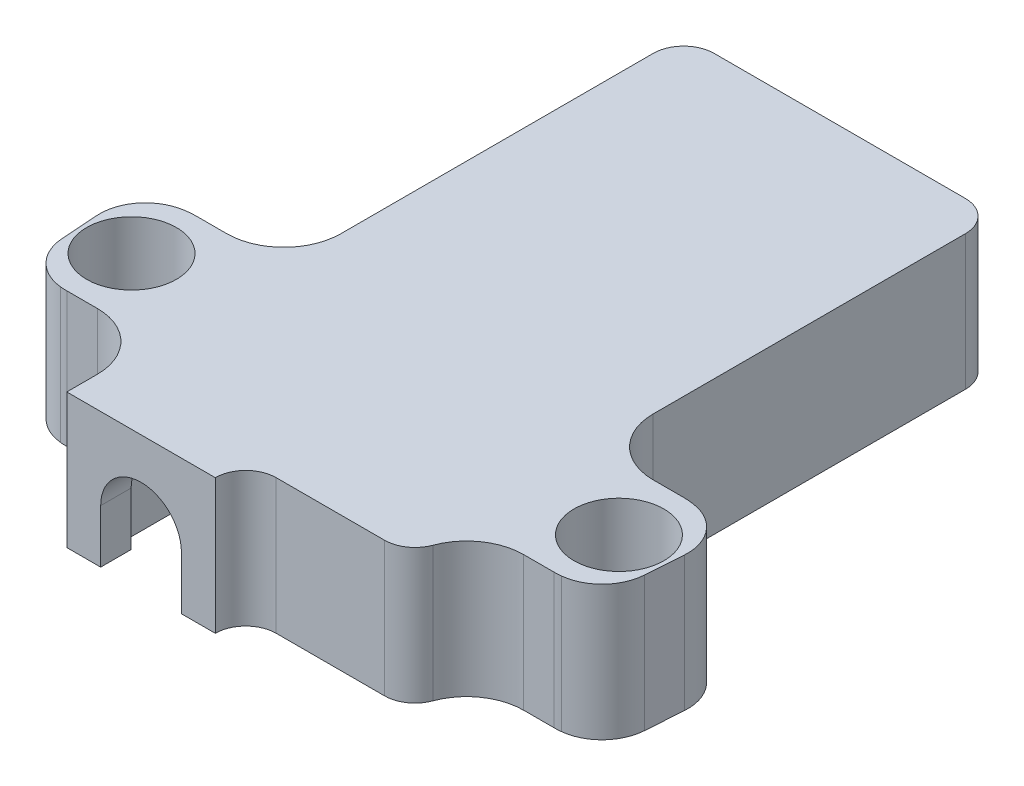
SolidWorks part; units mm, degrees
ref_plane "Front Plane" through (0, 0, 0) normal (0, 0, 1) x (1, 0, 0)
ref_plane "Top Plane" through (0, 0, 0) normal (0, 1, 0) x (1, 0, 0)
ref_plane "Right Plane" through (0, 0, 0) normal (1, 0, 0) x (0, 0, -1)
sketch "Sketch1" plane through (0, 0, 0) normal (0, 1, 0) x (1, 0, 0)
  line L0 (-24.2603, 0) -> (21.0129, 0) construction
  line L1 (0, 32.3789) -> (0, -20.9174) construction
  line L2 (0, 30.5) -> (0, -8) construction
  line L3 (-10.25, 30.5) -> (10.25, 30.5)
  line L4 (-10.25, 30.5) -> (-10.25, -8)
  line L5 (-10.25, -8) -> (10.25, -8)
  line L6 (10.25, 30.5) -> (10.25, -8)
  line L7 (-16, 4.25) -> (-10.25, 4.25)
  line L8 (-16, -4.25) -> (-10.25, -4.25)
  line L9 (16, 4.25) -> (10.25, 4.25)
  line L10 (16, -4.25) -> (10.25, -4.25)
  circle A0 centre (-16, 0) radius 1.75
  circle A1 centre (16, 0) radius 1.75
  circle A2 centre (-16, 0) radius 4.25
  circle A3 centre (16, 0) radius 4.25
  dimension "D1" = 3.5
  dimension "D2" = 32
  dimension "D3" = 20.5
  dimension "D5" = 8
  dimension "D6" = 38.5
  dimension "D4" = 2.5
extrude "Boss-Extrude1" add sketch "Sketch1" along normal blind 1.5 contours L6 L3 L4 L5 | A2 L8 L4 L7 | A2 A0 | L10 A3 L9 L6 | A3 A1
sketch "Sketch2" plane through (0, 1.5, 0) normal (0, 1, 0) x (1, 0, 0)
  line L1 (-10.25, 30.5) -> (10.25, 30.5)
  line L2 (-10.25, 30.5) -> (-10.25, -8)
  line L3 (-10.25, -8) -> (10.25, -8)
  line L4 (10.25, 30.5) -> (10.25, -8)
extrude "Boss-Extrude2" add sketch "Sketch2" along normal offset from surface (7.35 mm away) 8.85 up to face at (0, 0, -3.75)
sketch "Sketch3" plane through (0, 0, 0) normal (0, -1, 0) x (1, 0, 0)
  line L0 (-10.25, 8) -> (10.25, 8) construction
  line L1 (-8.75, 6.5) -> (8.75, 6.5)
  line L2 (-8.75, 6.5) -> (-8.75, -29)
  line L3 (-8.75, -29) -> (8.75, -29)
  line L4 (8.75, 6.5) -> (8.75, -29)
  line L5 (-10.25, -30.5) -> (10.25, -30.5) construction
  line L6 (-10.25, -30.5) -> (-10.25, -4.25) construction
  line L7 (10.25, -30.5) -> (10.25, -4.25) construction
  line L8 (-8.75, 6.5) -> (-8.75, 8)
  line L9 (-2, 6.5) -> (-2, 8)
  line M8 (10.25, 8) -> (-10.25, 8)
  dimension "D1" = 1.5
  dimension "D2" = 1.5
  dimension "D3" = 1.5
  dimension "D4" = 1.5
  dimension "D5" = 6.75
extrude "Cut-Extrude1" cut sketch "Sketch3" against normal offset from surface (7.35 mm away) 1.5 contours L4 L1 L2 L3 | L1 L9 L8 M8 up to face at (0, 8.85, -11.25)
sketch "Sketch4" plane through (0, 0, 0) normal (0, -1, 0) x (1, 0, 0)
  line L0 (-6.45, -29) -> (-6.45, -30.5)
  line L1 (-8.75, -29) -> (8.75, -29) construction
  line L2 (-10.25, -30.5) -> (10.25, -30.5) construction
  line L3 (0.75, -29) -> (0.75, -30.5)
  line L4 (-8.75, 8) -> (-8.75, -29) construction
  line L5 (-6.45, -29) -> (0.75, -29)
  line L6 (-6.45, -30.5) -> (0.75, -30.5)
  dimension "D1" = 2.3
  dimension "D2" = 7.2
extrude "Cut-Extrude2" cut sketch "Sketch4" against normal offset from surface (4.05 mm away) 3.3 up to face at (-0.6667, 7.35, -4.8333)
sketch "Sketch6" plane through (0, 7.35, 0) normal (0, -1, 0) x (1, 0, 0)
  line L0 (8.75, 6.5) -> (8.75, -29) construction
  line L1 (-8.75, -29) -> (8.75, -29)
  line L2 (-8.75, -29) -> (-8.75, -27.5)
  line L3 (-8.75, -27.5) -> (8.75, -27.5)
  line L4 (8.75, -29) -> (8.75, -27.5)
  dimension "D1" = 1.5
extrude "Boss-Extrude3" add sketch "Sketch6" along normal blind 1.35
sketch "Sketch7" plane through (0, 0, -29) normal (0, 0, 1) x (1, 0, 0)
  line L0 (8.75, 6) -> (8.75, 0) construction
  line L1 (8.75, 4.25) -> (5.25, 4.25)
  line L2 (8.75, 4.25) -> (8.75, 2.25)
  line L3 (8.75, 2.25) -> (5.25, 2.25)
  line L4 (5.25, 4.25) -> (5.25, 2.25)
  line L5 (-8.75, 6) -> (8.75, 6) construction
  dimension "D1" = 1.75
  dimension "D2" = 3.5
  dimension "D3" = 2
extrude "Boss-Extrude4" add sketch "Sketch7" along normal blind 1
sketch "Sketch8" plane through (0, 1.5, 0) normal (0, 1, 0) x (1, 0, 0)
  line L3 (-10.25, -4.25) -> (-10.25, 4.25)
  line L4 (-10.25, 4.25) -> (-16, 4.25)
  line L5 (-16, -4.25) -> (-10.25, -4.25)
  line L6 (-10.25, -4.25) -> (-10.25, 4.25)
  line L7 (-10.25, 4.25) -> (-16, 4.25)
  line L8 (-16, -4.25) -> (-10.25, -4.25)
  line L9 (10.25, 4.25) -> (10.25, -4.25)
  line L10 (10.25, -4.25) -> (16, -4.25)
  line L11 (16, 4.25) -> (10.25, 4.25)
  line L12 (10.25, 4.25) -> (10.25, -4.25)
  line L13 (10.25, -4.25) -> (16, -4.25)
  line L14 (16, 4.25) -> (10.25, 4.25)
  circle A0 centre (-16, 0) radius 2.95
  circle A1 centre (16, 0) radius 2.95
  arc A5 (-16, 4.25) -> (-16, -4.25) centre (-16, 0) ccw
  arc A8 (-16, 4.25) -> (-16, -4.25) centre (-16, 0) ccw
  arc A11 (16, -4.25) -> (16, 4.25) centre (16, 0) ccw
  arc A14 (16, -4.25) -> (16, 4.25) centre (16, 0) ccw
  dimension "D1" = 5.9
  dimension "D2" = 0
  dimension "D3" = 0
extrude "Boss-Extrude5" add sketch "Sketch8" along normal up to surface (7.35 mm away)
fillet "Fillet2" radius 3.75 4 edges
sketch "Sketch9" plane through (0, 8.85, 0) normal (0, 1, 0) x (1, 0, 0)
  line L0 (-24.9829, 53.6863) -> (-20.9528, -3.9479)
  line L1 (-15.1854, -10.3533) -> (-1.2155, -12.8165)
  line L2 (1.2155, -12.8165) -> (15.1854, -10.3533)
  line L3 (20.9528, -3.9479) -> (24.9829, 53.6863)
  line L4 (25, 54.1746) -> (25, 107.8254)
  line L5 (24.9829, 108.3137) -> (20.9528, 165.9479)
  line L6 (15.1854, 172.3533) -> (1.2155, 174.8165)
  line L7 (-1.2155, 174.8165) -> (-15.1854, 172.3533)
  line L8 (-20.9528, 165.9479) -> (-24.9829, 108.3137)
  line L9 (-25, 107.8254) -> (-25, 54.1746)
  line L10 (-18.9576, 165.8084) -> (-22.9878, 108.1742)
  line L11 (-23, 107.8254) -> (-23, 54.1746)
  line L12 (-22.9878, 53.8258) -> (-18.9576, -3.8084)
  line L13 (-14.8381, -8.3836) -> (-0.8682, -10.8469)
  line L14 (0.8682, -10.8469) -> (14.8381, -8.3836)
  line L15 (18.9576, -3.8084) -> (22.9878, 53.8258)
  line L16 (23, 54.1746) -> (23, 107.8254)
  line L17 (22.9878, 108.1742) -> (18.9576, 165.8084)
  line L18 (14.8381, 170.3836) -> (0.8682, 172.8469)
  line L19 (-0.8682, 172.8469) -> (-14.8381, 170.3836)
  line L20 (-18.9576, 165.8084) -> (-22.9878, 108.1742)
  line L21 (-23, 107.8254) -> (-23, 54.1746)
  line L22 (-22.9878, 53.8258) -> (-18.9576, -3.8084)
  line L23 (-14.8381, -8.3836) -> (-0.8682, -10.8469)
  line L24 (0.8682, -10.8469) -> (14.8381, -8.3836)
  line L25 (18.9576, -3.8084) -> (22.9878, 53.8258)
  line L26 (23, 54.1746) -> (23, 107.8254)
  line L27 (22.9878, 108.1742) -> (18.9576, 165.8084)
  line L28 (14.8381, 170.3836) -> (0.8682, 172.8469)
  line L29 (-0.8682, 172.8469) -> (-14.8381, 170.3836)
  arc A0 (-20.9528, -3.9479) -> (-15.1854, -10.3533) centre (-13.9698, -3.4596) ccw
  arc A1 (-1.2155, -12.8165) -> (1.2155, -12.8165) centre (0, -5.9229) ccw
  arc A2 (15.1854, -10.3533) -> (20.9528, -3.9479) centre (13.9698, -3.4596) ccw
  arc A3 (24.9829, 53.6863) -> (25, 54.1746) centre (18, 54.1746) ccw
  arc A4 (25, 107.8254) -> (24.9829, 108.3137) centre (18, 107.8254) ccw
  arc A5 (20.9528, 165.9479) -> (15.1854, 172.3533) centre (13.9698, 165.4596) ccw
  arc A6 (1.2155, 174.8165) -> (-1.2155, 174.8165) centre (0, 167.9229) ccw
  arc A7 (-15.1854, 172.3533) -> (-20.9528, 165.9479) centre (-13.9698, 165.4596) ccw
  arc A8 (-24.9829, 108.3137) -> (-25, 107.8254) centre (-18, 107.8254) ccw
  arc A9 (-25, 54.1746) -> (-24.9829, 53.6863) centre (-18, 54.1746) ccw
  arc A10 (-14.8381, 170.3836) -> (-18.9576, 165.8084) centre (-13.9698, 165.4596) ccw
  arc A11 (-22.9878, 108.1742) -> (-23, 107.8254) centre (-18, 107.8254) ccw
  arc A12 (-23, 54.1746) -> (-22.9878, 53.8258) centre (-18, 54.1746) ccw
  arc A13 (-18.9576, -3.8084) -> (-14.8381, -8.3836) centre (-13.9698, -3.4596) ccw
  arc A14 (-0.8682, -10.8469) -> (0.8682, -10.8469) centre (0, -5.9229) ccw
  arc A15 (14.8381, -8.3836) -> (18.9576, -3.8084) centre (13.9698, -3.4596) ccw
  arc A16 (22.9878, 53.8258) -> (23, 54.1746) centre (18, 54.1746) ccw
  arc A17 (23, 107.8254) -> (22.9878, 108.1742) centre (18, 107.8254) ccw
  arc A18 (18.9576, 165.8084) -> (14.8381, 170.3836) centre (13.9698, 165.4596) ccw
  arc A19 (0.8682, 172.8469) -> (-0.8682, 172.8469) centre (0, 167.9229) ccw
  arc A20 (-14.8381, 170.3836) -> (-18.9576, 165.8084) centre (-13.9698, 165.4596) ccw
  arc A21 (-22.9878, 108.1742) -> (-23, 107.8254) centre (-18, 107.8254) ccw
  arc A22 (-23, 54.1746) -> (-22.9878, 53.8258) centre (-18, 54.1746) ccw
  arc A23 (-18.9576, -3.8084) -> (-14.8381, -8.3836) centre (-13.9698, -3.4596) ccw
  arc A24 (-0.8682, -10.8469) -> (0.8682, -10.8469) centre (0, -5.9229) ccw
  arc A25 (14.8381, -8.3836) -> (18.9576, -3.8084) centre (13.9698, -3.4596) ccw
  arc A26 (22.9878, 53.8258) -> (23, 54.1746) centre (18, 54.1746) ccw
  arc A27 (23, 107.8254) -> (22.9878, 108.1742) centre (18, 107.8254) ccw
  arc A28 (18.9576, 165.8084) -> (14.8381, 170.3836) centre (13.9698, 165.4596) ccw
  arc A29 (0.8682, 172.8469) -> (-0.8682, 172.8469) centre (0, 167.9229) ccw
  dimension "D1" = 0
  dimension "D2" = 2
extrude "Cut-Extrude4" cut sketch "Sketch9" against normal up to next
fillet "Fillet5" radius 3 4 edges at (19.0145, 4.425, 2.9959) (19.4021, 4.425, -2.5472) (-19.0145, 4.425, 2.9959) (-19.4021, 4.425, -2.5472)
sketch "Sketch10" plane through (0, 0, 0) normal (0, 1, 0) x (1, 0, 0)
  line L0 (-2, -6.5) -> (-2, -8) construction
  line L1 (-10.25, -8) -> (-0.5, -8)
  line L2 (-10.25, -8) -> (-10.25, -10)
  line L3 (-10.25, -10) -> (-0.5, -10)
  line L4 (-0.5, -8) -> (-0.5, -10)
  dimension "D1" = 1.5
  dimension "D2" = 2
extrude "Boss-Extrude6" add sketch "Sketch10" along normal up to surface (8.85 mm away) up to face at (-16, 8.85, 2.95)
sketch "Sketch11" plane through (0, 0, 10) normal (0, 0, 1) x (1, 0, 0)
  line L0 (-5.375, 8.85) -> (-5.375, 0) construction
  line L1 (-10.25, 8.85) -> (-0.5, 8.85) construction
  line L2 (-10.25, 0) -> (-0.5, 0) construction
  line L3 (-2.725, 3.5) -> (-2.725, 0)
  line L4 (-8.025, 3.5) -> (-8.025, 0)
  circle A0 centre (-5.375, 3.5) radius 2.65
  line M3 (-10.25, 0) -> (-0.5, 0)
  dimension "D1" = 5.3
  dimension "D2" = 3.5
extrude "Cut-Extrude5" cut sketch "Sketch11" against normal up to next contours L0 A0 | A0 L0 | L0 A0 L4 M3 | A0 L0 L3 M3
fillet "Fillet4" radius 2 4 edges at (10.25, 4.425, 8) (10.25, 4.425, -30.5) (-10.25, 4.425, -30.5)
